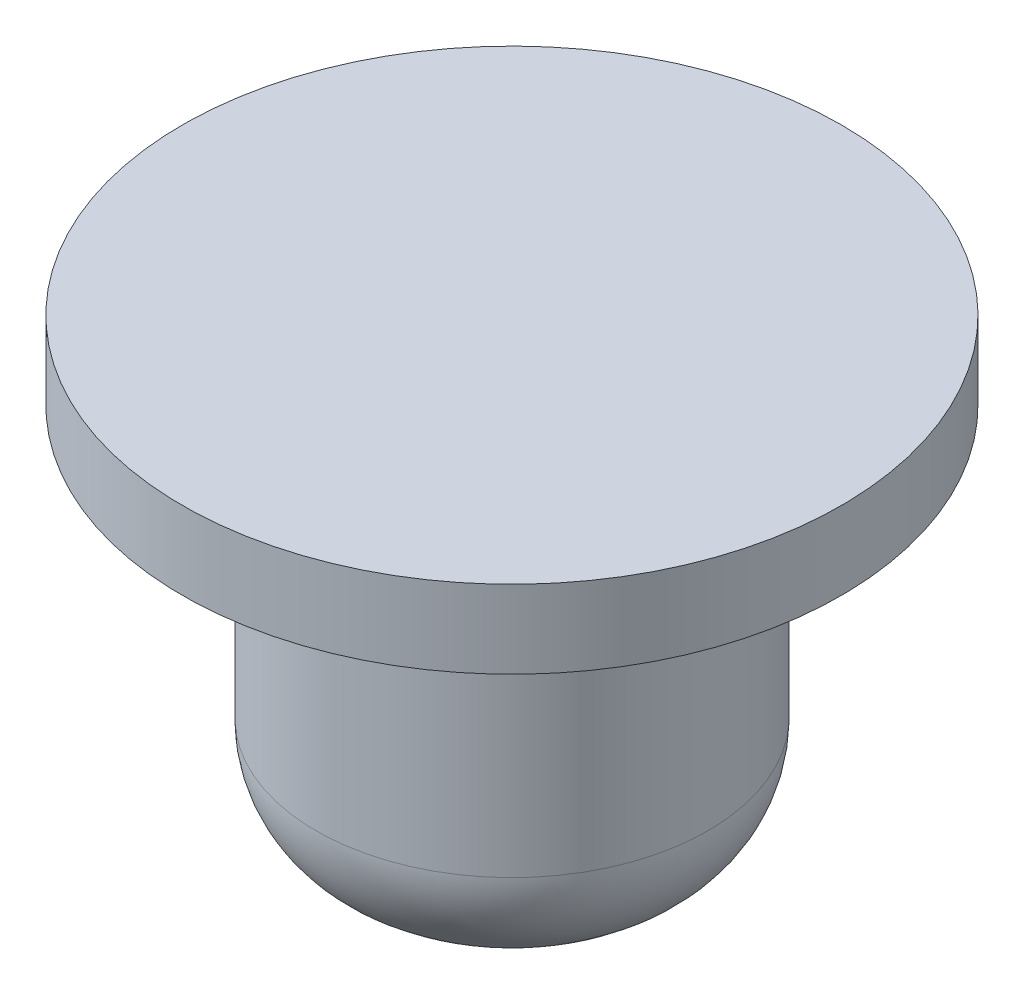
SolidWorks part; units mm, degrees
ref_plane "Front Plane" through (0, 0, 0) normal (0, 0, 1) x (1, 0, 0)
ref_plane "Top Plane" through (0, 0, 0) normal (0, 1, 0) x (1, 0, 0)
ref_plane "Right Plane" through (0, 0, 0) normal (1, 0, 0) x (0, 0, -1)
sketch "Sketch1" plane through (0, 0, 0) normal (0, 0, 1) x (1, 0, 0)
  line L0 (0, 7.5525) -> (10.6796, 7.5525)
  line L1 (10.6796, 7.5525) -> (10.6796, 5.0274)
  line L2 (10.6796, 5.0274) -> (6.35, 5.0274)
  line L3 (6.35, 5.0274) -> (6.35, -3.7425)
  line L4 (2.54, -7.5525) -> (0, -7.5525)
  line L5 (0, -7.5525) -> (0, 7.5525)
  arc A0 (6.35, -3.7425) -> (2.54, -7.5525) centre (2.54, -3.7425) cw
  point P9 (6.35, -7.5525)
  point P10 (0, 0)
  dimension "D2" = 3.81
  dimension "D1" = 6.35
revolve "Revolve1" add sketch "Sketch1" angle 360 about L5
sketch "Sketch2" plane through (0, 0, 0) normal (0, 0, 1) x (1, 0, 0)
  line L1 (-36.4156, 0) -> (36.4156, 0)
  line L2 (-36.4156, 0) -> (-36.4156, 20.9525)
  line L3 (-36.4156, 20.9525) -> (36.4156, 20.9525)
  line L4 (36.4156, 0) -> (36.4156, 20.9525)
extrude "Cut-Extrude1" [suppressed] cut sketch "Sketch2" against normal through all both and the other way through all
